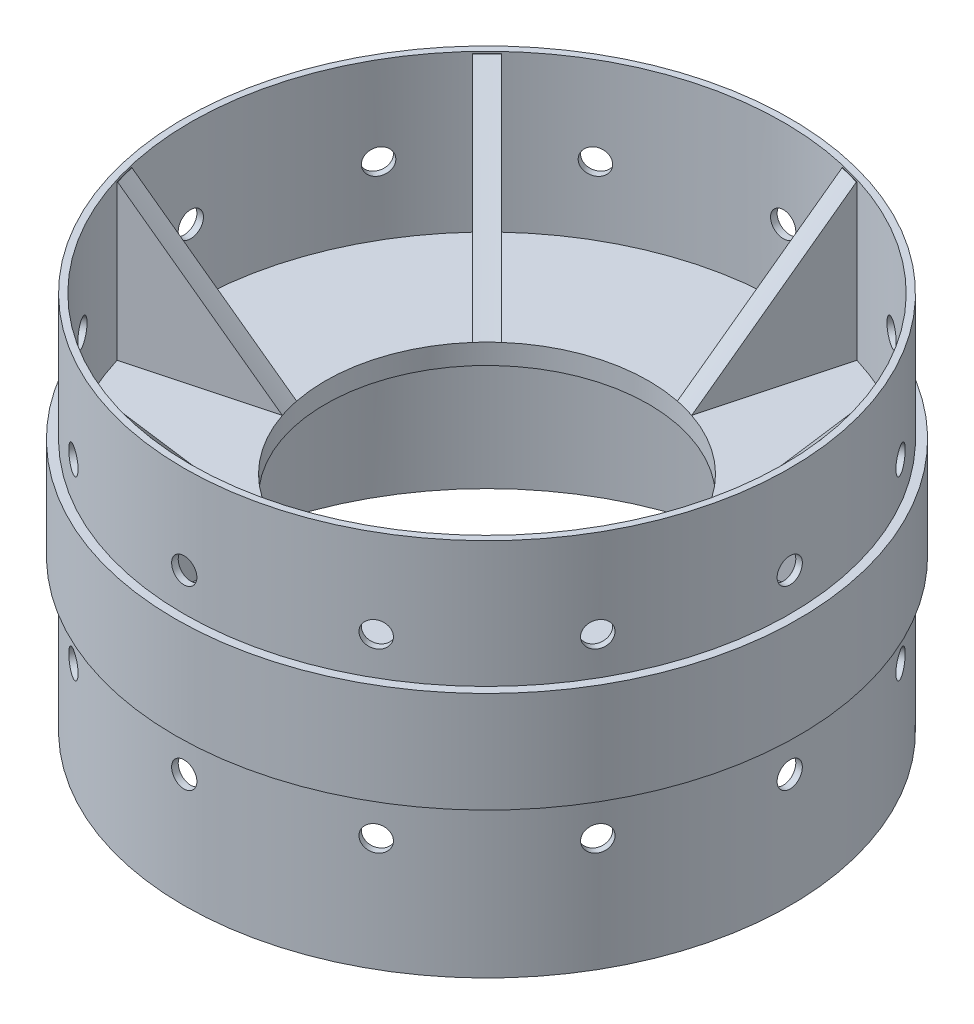
SolidWorks part; units mm, degrees
material "2024-T4"
ref_plane "Front Plane" through (0, 0, 0) normal (0, 0, 1) x (1, 0, 0)
ref_plane "Top Plane" through (0, 0, 0) normal (0, 1, 0) x (1, 0, 0)
ref_plane "Right Plane" through (0, 0, 0) normal (1, 0, 0) x (0, 0, -1)
sketch "Sketch1" plane through (0, 0, 0) normal (0, 1, 0) x (1, 0, 0)
  circle A0 centre (0, 0) radius 74.549
  circle A1 centre (0, 0) radius 78.359
  dimension "D1" = 149.098
  dimension "D2" = 156.718
extrude "Boss-Extrude1" add sketch "Sketch1" along normal blind 25.4
sketch "Sketch2" plane through (0, 25.4, 0) normal (0, 1, 0) x (1, 0, 0)
  circle A0 centre (0, 0) radius 76.2
  circle A1 centre (0, 0) radius 74.549
extrude "Boss-Extrude2" add sketch "Sketch2" along normal blind 31.75
sketch "Sketch3" plane through (0, 0, 0) normal (0, -1, 0) x (1, 0, 0)
  circle A0 centre (0, 0) radius 76.2
  circle A1 centre (0, 0) radius 74.549
  dimension "D1" = 152.4
extrude "Boss-Extrude3" add sketch "Sketch3" along normal blind 38.1
ref_plane "Plane1" through (0, 12.7, 0) normal (0, 1, 0) x (1, 0, 0)
sketch "Sketch4" plane through (0, 12.7, 0) normal (0, 1, 0) x (1, 0, 0)
  circle A0 centre (0, 0) radius 74.549
  circle A1 centre (0, 0) radius 40.64
  dimension "D1" = 81.28
extrude "Boss-Extrude4" add sketch "Sketch4" along normal blind 5.08
sketch "Sketch5" plane through (0, 17.78, 0) normal (0, 1, 0) x (1, 0, 0)
  line L3 (0, 0) -> (40.64, 0) construction
  line L35 (38.5211, 12.9513) -> (71.3096, 21.737)
  line L36 (39.8359, 8.0444) -> (72.6244, 16.83)
  line L37 (72.0088, 19.2947) -> (0, 0) construction
  line L38 (26.8846, -30.4767) -> (50.8874, -54.4795)
  line L39 (30.4767, -26.8846) -> (54.4795, -50.8874)
  line L40 (-12.9513, -38.5211) -> (-21.737, -71.3096)
  line L41 (-8.0444, -39.8359) -> (-16.83, -72.6244)
  line L42 (-39.8359, -8.0444) -> (-72.6244, -16.83)
  line L43 (-38.5211, -12.9513) -> (-71.3096, -21.737)
  line L44 (-26.8846, 30.4767) -> (-50.8874, 54.4795)
  line L45 (-30.4767, 26.8846) -> (-54.4795, 50.8874)
  line L46 (12.9513, 38.5211) -> (21.737, 71.3096)
  line L47 (8.0444, 39.8359) -> (16.83, 72.6244)
  circle A0 centre (0, 0) radius 40.64 construction
  circle A3 centre (0, 0) radius 74.549 construction
  arc A34 (71.3096, 21.737) -> (72.6244, 16.83) centre (0, 0) cw
  arc A35 (38.5211, 12.9513) -> (39.8359, 8.0444) centre (0, 0) cw
  arc A36 (30.4767, -26.8846) -> (26.8846, -30.4767) centre (0, 0) cw
  arc A37 (54.4795, -50.8874) -> (50.8874, -54.4795) centre (0, 0) cw
  arc A38 (-8.0444, -39.8359) -> (-12.9513, -38.5211) centre (0, 0) cw
  arc A39 (-16.83, -72.6244) -> (-21.737, -71.3096) centre (0, 0) cw
  arc A40 (-38.5211, -12.9513) -> (-39.8359, -8.0444) centre (0, 0) cw
  arc A41 (-71.3096, -21.737) -> (-72.6244, -16.83) centre (0, 0) cw
  arc A42 (-30.4767, 26.8846) -> (-26.8846, 30.4767) centre (0, 0) cw
  arc A43 (-54.4795, 50.8874) -> (-50.8874, 54.4795) centre (0, 0) cw
  arc A44 (8.0444, 39.8359) -> (12.9513, 38.5211) centre (0, 0) cw
  arc A45 (16.83, 72.6244) -> (21.737, 71.3096) centre (0, 0) cw
  point P29 (0, 0)
  point P34 (0, 0)
  point P40 (0, 0)
  point P42 (39.2552, 10.5184)
  dimension "D1" = 15
  dimension "D2" = 6
  dimension "D5" = 5.08
extrude "Boss-Extrude10" add sketch "Sketch5" along normal blind 38.862
chamfer "Chamfer1" distance 38.862 distance2 33.782 6 edges at (-39.2552, 56.642, 10.5184) (-10.5184, 56.642, 39.2552) (28.7368, 56.642, 28.7368) (39.2552, 56.642, -10.5184) (10.5184, 56.642, -39.2552) (-28.7368, 56.642, -28.7368) first distance on face at (0, 37.211, 0)
sketch "Sketch7" plane through (0, 0, 0) normal (0, 0, 1) x (1, 0, 0)
  line L0 (0, 42.3302) -> (0, 74.728) construction
  line L1 (78.359, 25.4) -> (-78.359, 25.4) construction
  line L2 (-78.359, 12.7) -> (83.2334, 12.7) construction
  line L3 (-78.359, 25.4) -> (-78.359, 0) construction
  circle A0 centre (0, 34.925) radius 3.175
  circle A1 centre (0, -9.525) radius 3.175
  dimension "D1" = 6.35
  dimension "D2" = 9.525
extrude "Cut-Extrude2" cut sketch "Sketch7" against normal through all
ref_axis "Axis1" through (0, 42.3302, 0) along (0, 1, 0)
pattern_circular "CirPattern2" count 12 over 360 about axis through (0, 42.3302, 0) along (0, 1, 0) of "Cut-Extrude2"
